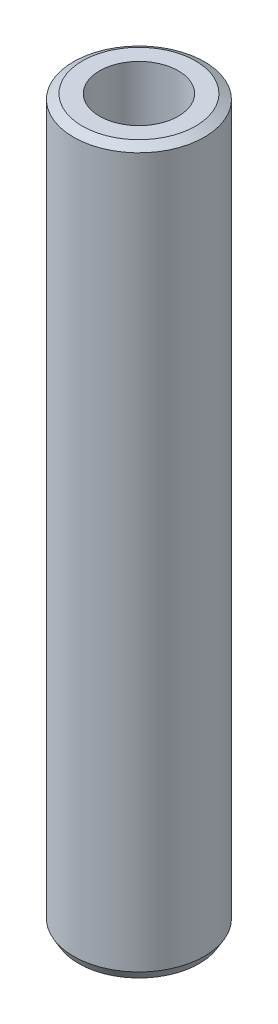
SolidWorks part; units mm, degrees
ref_plane "Front Plane" through (0, 0, 0) normal (0, 0, 1) x (1, 0, 0)
ref_plane "Top Plane" through (0, 0, 0) normal (0, 1, 0) x (1, 0, 0)
ref_plane "Right Plane" through (0, 0, 0) normal (1, 0, 0) x (0, 0, -1)
sketch "Sketch1" plane through (0, 0, 0) normal (0, 1, 0) x (1, 0, 0)
  circle A0 centre (0, 0) radius 30
  dimension "SHAFT_OD" = 60
extrude "Boss-Extrude1" add sketch "Sketch1" along normal blind 331.6265
sketch "Sketch2" plane through (0, 0, 0) normal (0, 1, 0) x (1, 0, 0)
  circle A0 centre (0, 0) radius 18.052
  dimension "BORE_D" = 36.104
extrude "Cut-Extrude1" cut sketch "Sketch2" along normal through all
chamfer "Chamfer1" distance 2.3441 angle 60 2 edges at (0, 331.6265, 30) (0, 0, 30) first distance on face at (0, 331.6265, 30) first distance on face at (0, 0, 18.052)
